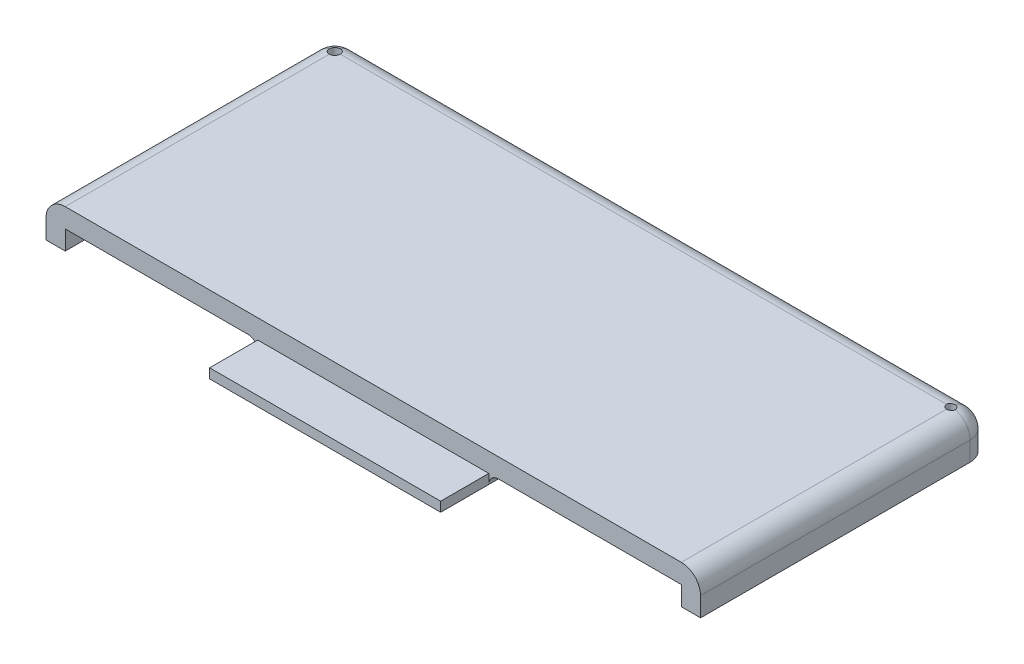
SolidWorks part; units mm, degrees
ref_plane "Front Plane" through (0, 0, 0) normal (0, 0, 1) x (1, 0, 0)
ref_plane "Top Plane" through (0, 0, 0) normal (0, 1, 0) x (1, 0, 0)
ref_plane "Right Plane" through (0, 0, 0) normal (1, 0, 0) x (0, 0, -1)
sketch "Sketch1" plane through (0, 0, 0) normal (0, 0, 1) x (1, 0, 0)
  line L1 (-85, 35) -> (85, 35)
  line L2 (-85, 35) -> (-85, -35)
  line L3 (-85, -35) -> (85, -35)
  line L4 (85, 35) -> (85, -35)
  line L5 (-85, 35) -> (85, -35) construction
  line L6 (-85, -35) -> (85, 35) construction
  point P0 (0, 0)
  dimension "D1" = 170
  dimension "D2" = 70
extrude "Boss-Extrude1" add sketch "Sketch1" along normal blind 90
fillet "Fillet2" radius 5 4 edges at (-85, 35, 45) (-85, -35, 45) (85, -35, 45) (85, 35, 45)
sketch "Sketch5" plane through (0, 0, 90) normal (0, 0, 1) x (1, 0, 0)
  circle A0 centre (-80, 30) radius 1.4
  circle A1 centre (-80, -30) radius 1.4
  circle A2 centre (80, 30) radius 1.4
  circle A4 centre (80, -30) radius 1.4
  dimension "D1" = 2.8
  dimension "D2" = 2.8
  dimension "D3" = 2.8
  dimension "D4" = 2.8
extrude "Cut-Extrude2" cut sketch "Sketch5" against normal blind 12
sketch "Sketch6" plane through (-85, 0, 0) normal (-1, 0, 0) x (0, 0, 1)
  line L1 (0, 35) -> (90, 35) construction
  line L3 (0, 30) -> (0, -30) construction
  line L4 (0, 25) -> (0, -35)
  line L5 (0, -35) -> (90, -35)
  line L6 (75, 35) -> (75, 25)
  line L7 (75, 25) -> (0, 25)
  line L8 (75, 35) -> (90, 35)
  line L9 (90, 35) -> (90, -35)
extrude "Cut-Extrude3" cut sketch "Sketch6" against normal blind 170
sketch "Sketch7" plane through (0, 0, 75) normal (0, 0, 1) x (1, 0, 0)
  line L1 (85, 25) -> (-85, 25) construction
  line L2 (-78.9423, 25) -> (-78.9423, 30)
  line L5 (80, 25) -> (80, 30)
  line L6 (80, 30) -> (-78.9423, 30)
  line L7 (-78.9423, 25) -> (80, 25)
extrude "Cut-Extrude4" cut sketch "Sketch7" against normal blind 70
sketch "Sketch9" plane through (0, 0, 75) normal (0, 0, 1) x (1, 0, 0)
  line L1 (-78.9423, 25) -> (-85, 25) construction
  line L2 (-80, 25) -> (-80, 30)
  line L3 (-80, 30) -> (-78.9423, 30)
  line L4 (-78.9423, 30) -> (-78.9423, 25)
  line L5 (-78.9423, 25) -> (80, 25) construction
  line L6 (-78.9423, 30) -> (-78.9423, 25) construction
  line L7 (-78.9423, 25) -> (-80, 25)
  line L9 (85, 25) -> (80, 25) construction
  line L10 (82.045, 25) -> (82.045, 30)
  line L11 (82.045, 30) -> (80, 30)
  line L12 (80, 30) -> (80, 25)
  line L13 (80, 25) -> (82.045, 25)
extrude "Cut-Extrude5" cut sketch "Sketch9" against normal blind 70
sketch "Sketch12" plane through (0, 0, 75) normal (0, 0, 1) x (1, 0, 0)
  line L1 (85, 25) -> (80, 25)
  line L2 (-80, 25) -> (82.045, 25) construction
  line L3 (80, 25) -> (80, 30)
  line L4 (82.045, 30) -> (-80, 30) construction
  line L5 (80, 30) -> (85, 30)
  line L6 (85, 30) -> (85, 25)
extrude "Boss-Extrude2" add sketch "Sketch12" against normal blind 75
sketch "Sketch13" plane through (0, 25, 0) normal (0, -1, 0) x (-1, 0, 0)
  circle A0 centre (-80, -5) radius 5
  circle A1 centre (80, -5) radius 5
extrude "Boss-Extrude4" add sketch "Sketch13" against normal blind 5
sketch "Sketch14" plane through (0, 25, 0) normal (0, -1, 0) x (1, 0, 0)
  circle A0 centre (-80, 5) radius 1.4
  circle A1 centre (80, 5) radius 1.1158
extrude "Cut-Extrude6" cut sketch "Sketch14" against normal blind 10
fillet "Fillet3" radius 5 5 edges at (0, 35, 0) (83.5355, 33.5355, 0) (85, 27.5, 0) (-83.5355, 33.5355, 0) (-85, 27.5, 0)
sketch "Sketch15" plane through (0, 30, 0) normal (0, -1, 0) x (1, 0, 0)
  line L0 (0, 75) -> (30, 75)
  line L1 (80, 75) -> (-80, 75) construction
  line L2 (30, 75) -> (30, 67.5)
  line L3 (30, 67.5) -> (-30, 67.5)
  line L4 (-30, 67.5) -> (-30, 75)
  line L5 (-30, 75) -> (0, 75)
  dimension "D1" = 30
  dimension "D2" = 30
  dimension "D3" = 7.5
extrude "Boss-Extrude5" add sketch "Sketch15" along normal blind 2.5
sketch "Sketch16" plane through (0, 0, 75) normal (0, 0, 1) x (1, 0, 0)
  line L0 (30, 30) -> (30, 27.5)
  line L1 (75, 30) -> (-75, 30) construction
  line L2 (30, 27.5) -> (30, 30) construction
  line L3 (30, 27.5) -> (-30, 27.5)
  line L4 (30, 27.5) -> (-30, 27.5) construction
  line L5 (-30, 27.5) -> (-30, 30)
  line L6 (-30, 30) -> (30, 30)
extrude "Boss-Extrude6" add sketch "Sketch16" along normal blind 12.5
fillet "Fillet4" radius 2.5 3 edges at (-30, 30, 71.25) (0, 30, 67.5) (30, 30, 71.25)
